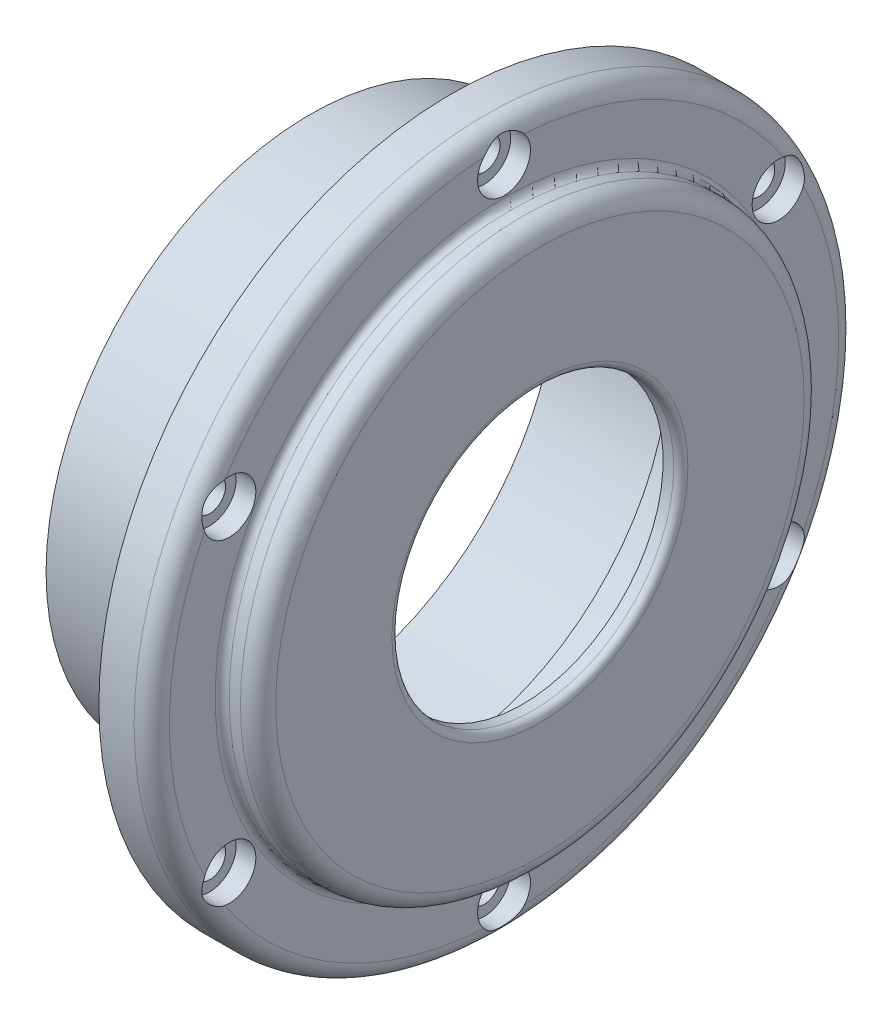
SolidWorks part; units mm, degrees
ref_plane "Front Plane" through (0, 0, 0) normal (0, 0, 1) x (1, 0, 0)
ref_plane "Top Plane" through (0, 0, 0) normal (0, 1, 0) x (1, 0, 0)
ref_plane "Right Plane" through (0, 0, 0) normal (1, 0, 0) x (0, 0, -1)
sketch "Sketch1" plane through (0, 0, 0) normal (0, 0, 1) x (1, 0, 0)
  line L0 (-15.2619, -33.1832) -> (53.5176, -33.1832)
  line L1 (22.9739, 66.8168) -> (37.9739, 66.8168)
  line L2 (-17.0261, 41.8168) -> (-17.0261, 36.8168)
  line L3 (43.1657, 6.8168) -> (48.1657, 6.8168)
  line L4 (48.1657, 46.8168) -> (48.1657, 6.8168)
  line L16 (-17.0261, 41.8168) -> (22.9739, 41.8168)
  line L17 (22.9739, 66.8168) -> (22.9739, 41.8168)
  line L20 (-17.0261, 36.8168) -> (17.9739, 36.8168)
  line L21 (17.9739, 33.8168) -> (17.9739, 36.8168)
  line L22 (17.9739, 33.8168) -> (35.1657, 33.8168)
  line L25 (43.1657, 21.8168) -> (43.1657, 6.8168)
  line L28 (48.1657, 46.8168) -> (37.9739, 46.8168)
  line L29 (37.9739, 66.8168) -> (37.9739, 46.8168)
  line L32 (43.1657, 21.8168) -> (35.1657, 21.8168)
  line L33 (35.1657, 33.8168) -> (35.1657, 21.8168)
  dimension "D1" = 60
  dimension "D2" = 40
  dimension "D3" = 40
  dimension "D4" = 35
  dimension "D5" = 3
  dimension "D6" = 5
  dimension "D7" = 15
  dimension "D8" = 5
  dimension "D9" = 30
  dimension "D10" = 12
  dimension "D11" = 8
  dimension "D12" = 25.1918
revolve "Revolve1" add sketch "Sketch1" angle 360 about L0 region at (29.4531, 41.0387, 0)
sketch "Sketch2" plane through (37.9739, 0, 0) normal (1, 0, 0) x (0, 0, -1)
  line L0 (0, -33.1832) -> (0, 56.8168)
  line L1 (0, -33.1832) -> (77.9423, 11.8168)
  line L2 (0, -33.1832) -> (77.9423, -78.1832)
  line L3 (0, -33.1832) -> (0, -123.1832)
  line L4 (0, -33.1832) -> (-77.9423, -78.1832)
  line L5 (0, -33.1832) -> (-77.9423, 11.8168)
  point P6 (0, 56.8168)
  point P9 (0, -33.1832)
  point P24 (-77.9423, 11.8168)
  point P27 (-77.9423, -78.1832)
  point P30 (0, -123.1832)
  point P33 (77.9423, -78.1832)
  point P36 (77.9423, 11.8168)
  point P37 (0, 0)
  point P38 (0, 0)
  dimension "D1" = 90
  dimension "D2" = 6
hole_wizard "CBORE for M8 Hex Socket Thin Head Cap Screw1" positions "Sketch2" profile "Sketch3" counterbore size "M8" standard "DIN"
sketch "Sketch3" plane through (37.9739, 11.8168, -77.9423) normal (0, 1, 0) x (0, 0, -1)
  line L0 (0, 0) -> (0, 17.7039)
  line L1 (0, 17.7039) -> (4.5, 15)
  line L2 (4.5, 15) -> (4.5, 5.6)
  line L3 (4.5, 5.6) -> (7.5, 5.6)
  line L4 (7.5, 5.6) -> (7.5, 0)
  line L5 (7.5, 0) -> (0, 0)
  line L10 (0, 17.7039) -> (-4.5, 15) construction
  line L11 (0, -6.35) -> (0, 107.95) construction
  dimension "Hole Dia." = 9
  dimension "Hole Depth" = 15
  dimension "C'Bore Dia." = 15
  dimension "C'Bore Depth" = 5.6
  dimension "Drill Angle" = 118
fillet "Fillet1" radius 2 2 edges at (37.9739, -33.1832, 80) (48.1657, -33.1832, 40)
fillet "Fillet2" radius 5 2 edges at (37.9739, -33.1832, 100) (48.1657, -33.1832, 80)
